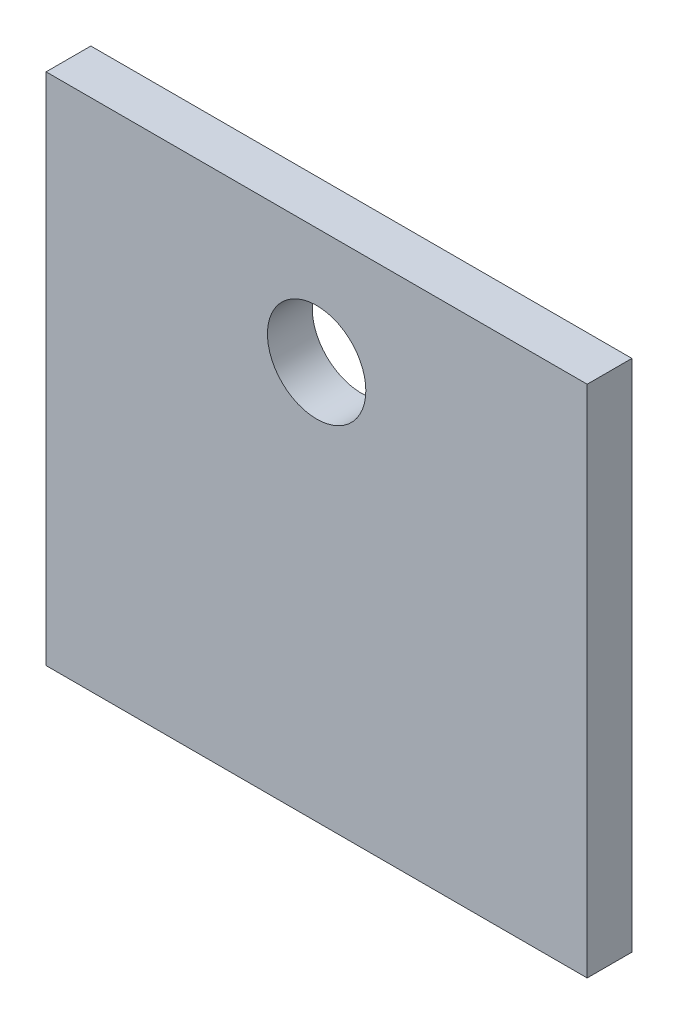
SolidWorks part; units mm, degrees
ref_plane "Front Plane" through (0, 0, 0) normal (0, 0, 1) x (1, 0, 0)
ref_plane "Top Plane" through (0, 0, 0) normal (0, 1, 0) x (1, 0, 0)
ref_plane "Right Plane" through (0, 0, 0) normal (1, 0, 0) x (0, 0, -1)
sketch "Sketch1" plane through (0, 0, 0) normal (0, 0, 1) x (1, 0, 0)
  line L1 (12.1, -11.5) -> (-12.1, -11.5)
  line L2 (12.1, -11.5) -> (12.1, 11.5)
  line L3 (12.1, 11.5) -> (-12.1, 11.5)
  line L4 (-12.1, -11.5) -> (-12.1, 11.5)
  line L5 (12.1, -11.5) -> (-12.1, 11.5) construction
  line L6 (12.1, 11.5) -> (-12.1, -11.5) construction
  point P0 (0, 0)
  dimension "D1" = 24.2
  dimension "D2" = 23
extrude "Boss-Extrude1" add sketch "Sketch1" along normal blind 2
sketch "Sketch2" plane through (0, 0, 2) normal (0, 0, 1) x (1, 0, 0)
  line L2 (12.1, 11.5) -> (-12.1, 11.5) construction
  line L3 (-12.1, 11.5) -> (-12.1, -11.5) construction
  circle A0 centre (0, 6.3) radius 2.2
  point P3 (0, 0)
  dimension "D1" = 4.4
  dimension "D2" = 5.2
  dimension "D3" = 12.1
extrude "Cut-Extrude1" cut sketch "Sketch2" against normal blind 2
